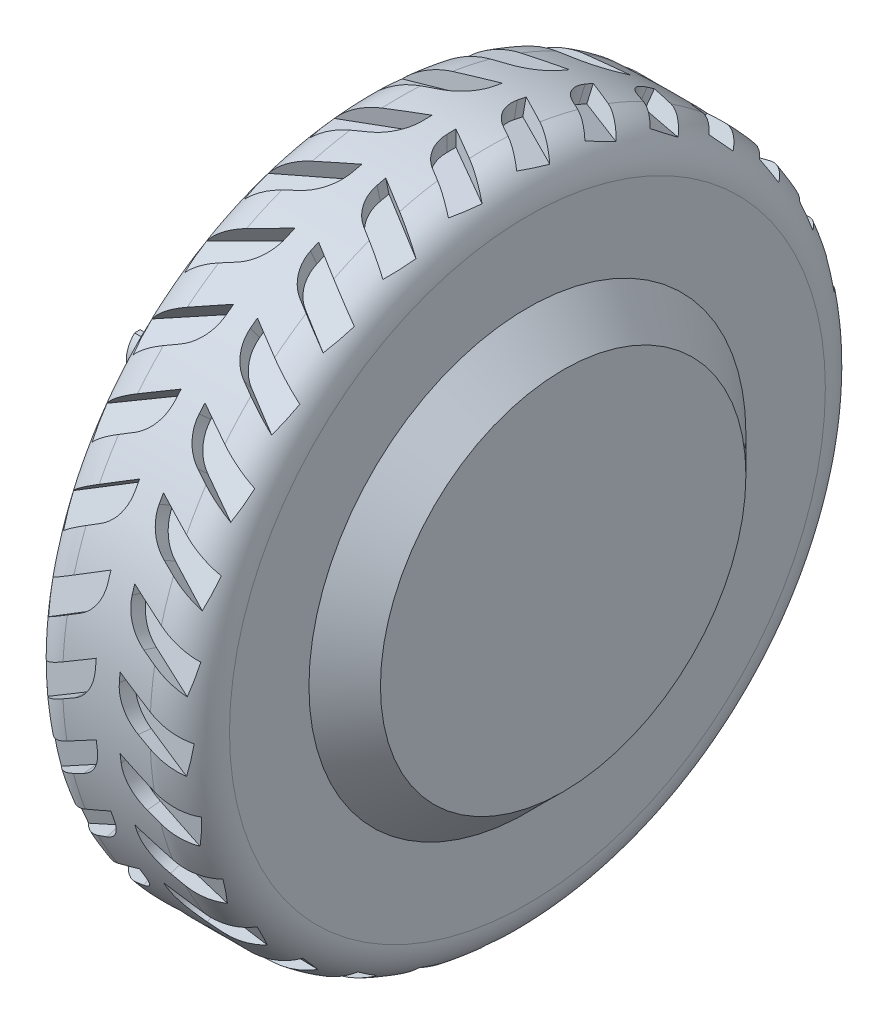
SolidWorks part; units mm, degrees
material "1.6566 (17NiCrMo6-4)"
ref_plane "前视基准面" through (0, 0, 0) normal (0, 0, 1) x (1, 0, 0)
ref_plane "上视基准面" through (0, 0, 0) normal (0, 1, 0) x (1, 0, 0)
ref_plane "右视基准面" through (0, 0, 0) normal (1, 0, 0) x (0, 0, -1)
sketch "草图1" plane through (0, 0, 0) normal (1, 0, 0) x (0, 0, -1)
  circle A0 centre (0, 0) radius 85
  dimension "D1" = 170
extrude "凸台-拉伸1" add sketch "草图1" along normal mid plane 42
sketch "草图2" plane through (21, 0, 0) normal (1, 0, 0) x (0, 0, -1)
  circle A0 centre (0, 0) radius 55
  dimension "D1" = 110
extrude "凸台-拉伸2" add sketch "草图2" along normal blind 9
chamfer "倒角1" distance 9 angle 45 1 edges at (30, 0, -55)
fillet "圆角1" radius 10 2 edges at (21, 0, -85) (-21, 0, -85)
ref_plane "基准面4" through (0, 85, 0) normal (0, 1, 0) x (1, 0, 0)
sketch "草图4" plane through (0, 85, 0) normal (0, 1, 0) x (1, 0, 0)
  line L0 (3, 0) -> (37.9736, 0) construction
  line L1 (3, 0) -> (3, -2.2265)
  line L2 (8, -10.8868) -> (21, -18.3923)
  line L3 (21, -85) -> (21, 85) construction
  line L4 (21, -18.3923) -> (21, -10.3923)
  line L6 (21, -10.3923) -> (3, 0)
  arc A0 (3, -2.2265) -> (8, -10.8868) centre (13, -2.2265) ccw
  dimension "D3" = 10
  dimension "D1" = 8
  dimension "D2" = 30
  dimension "D4" = 3
extrude "切除-拉伸2" cut sketch "草图4" against normal blind 4
pattern_circular "阵列(圆周)1" count 30 over 360 about axis through (21, 0, 0) along (1, 0, 0) of "切除-拉伸2"
mirror "镜向1" about plane through (0, 0, 0) normal (1, 0, 0) of "阵列(圆周)1", "凸台-拉伸2", "倒角1"
sketch "草图6" plane through (-30, 0, 0) normal (-1, 0, 0) x (0, 0, 1)
  circle A0 centre (0, 0) radius 7
  dimension "D1" = 14
extrude "凸台-拉伸3" add sketch "草图6" along normal blind 43
sketch "草图7" plane through (-73, 0, 0) normal (-1, 0, 0) x (0, 0, 1)
  line L0 (-4.899, 5) -> (4.899, 5)
  line L1 (0, 0) -> (-26.6769, 0) construction
  line L2 (-4.899, -5) -> (4.899, -5)
  arc A0 (-4.899, -5) -> (4.899, -5) centre (0, 0) ccw
  circle A1 centre (0, 0) radius 7
  arc A2 (4.899, 5) -> (-4.899, 5) centre (0, 0) ccw
  dimension "D2" = 10
  dimension "D1" = 0
extrude "切除-拉伸3" cut sketch "草图7" against normal blind 38
sketch "草图8" plane through (0, 5, 0) normal (0, 1, 0) x (1, 0, 0)
  line L1 (-73, 0) -> (-70, 0) construction
  line L2 (-73, 4.899) -> (-73, -4.899) construction
  line L3 (-73, 3.5) -> (-70, 3.5)
  line L4 (-73, -3.5) -> (-70, -3.5)
  arc A1 (-73, 3.5) -> (-73, -3.5) centre (-73, 0) ccw
  arc A2 (-70, -3.5) -> (-70, 3.5) centre (-70, 0) ccw
  point P5 (-71.5, 0)
  dimension "D1" = 3.5
  dimension "D2" = 3
extrude "切除-拉伸4" cut sketch "草图8" along direction (0, 1, 0) on the side against the normal up to surface (5 mm away) up to plane "上视基准面"
